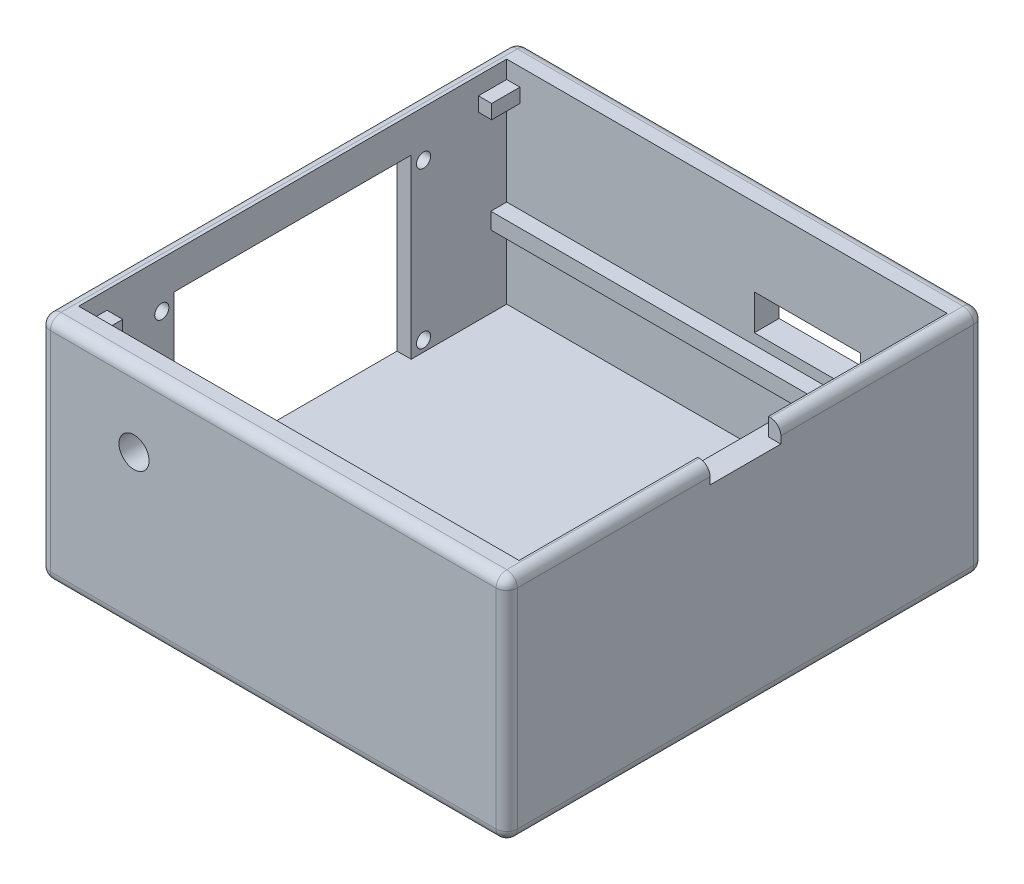
SolidWorks part; units mm, degrees
ref_plane "Front Plane" through (0, 0, 0) normal (0, 0, 1) x (1, 0, 0)
ref_plane "Top Plane" through (0, 0, 0) normal (0, 1, 0) x (1, 0, 0)
ref_plane "Right Plane" through (0, 0, 0) normal (1, 0, 0) x (0, 0, -1)
sketch "Sketch2" plane through (0, 0, 0) normal (0, 1, 0) x (1, 0, 0)
  line L0 (-60.5, 60.5) -> (-60.5, -60.5)
  line L1 (-67.5, 67.5) -> (67.5, 67.5)
  line L2 (-67.5, 67.5) -> (-67.5, -67.5)
  line L3 (-67.5, -67.5) -> (67.5, -67.5)
  line L4 (67.5, 67.5) -> (67.5, -67.5)
  line L5 (-67.5, 67.5) -> (67.5, -67.5) construction
  line L6 (-67.5, -67.5) -> (67.5, 67.5) construction
  line L7 (-60.5, -60.5) -> (60.5, -60.5)
  line L8 (60.5, 60.5) -> (60.5, -60.5)
  line L9 (-60.5, 60.5) -> (60.5, 60.5)
  point P0 (0, 0)
  dimension "D1" = 135
  dimension "D2" = 135
  dimension "D3" = 7
extrude "Boss-Extrude1" add sketch "Sketch2" along normal blind 65
extrude "Boss-Extrude2" add sketch "Sketch2<2>" along normal blind 5 contours L9 L0 L7 L8 region at (0, 0, 0)
sketch "Sketch2<2>" plane through (0, 0, 0) normal (0, 1, 0) x (1, 0, 0) same geometry as "Sketch2"
sketch "Sketch3" plane through (0, 0, -60.5) normal (0, 0, 1) x (1, 0, 0)
  line L1 (0, 0) -> (0, 65) construction
  line L2 (67.5, 0) -> (-67.5, 0) construction
  line L3 (60.5, 65) -> (-60.5, 65) construction
  line L4 (60.5, 65) -> (60.5, 5) construction
  line L5 (-60.5, 25.4157) -> (60.5, 25.4157)
  line L6 (-60.5, 25.4157) -> (-60.5, 30)
  line L7 (-60.5, 30) -> (60.5, 30)
  line L8 (60.5, 25.4157) -> (60.5, 30)
  line L9 (-60.5, 25.4157) -> (60.5, 30) construction
  line L10 (-60.5, 30) -> (60.5, 25.4157) construction
  line L11 (-60.5, 5) -> (60.5, 5) construction
  line L12 (-60.5, 65) -> (-60.5, 5) construction
  line L13 (9.5, 43) -> (39.5, 43)
  line L14 (9.5, 43) -> (9.5, 33)
  line L15 (9.5, 33) -> (39.5, 33)
  line L16 (39.5, 43) -> (39.5, 33)
  line L17 (9.5, 43) -> (39.5, 33) construction
  line L18 (9.5, 33) -> (39.5, 43) construction
  point P1 (0, 27.7078)
  point P16 (24.5, 38)
  dimension "D1" = 25
  dimension "D2" = 121
  dimension "D3" = 30
  dimension "D4" = 10
  dimension "D5" = 70
  dimension "D6" = 13
extrude "Boss-Extrude3" add sketch "Sketch3" along normal blind 4.5 contours L5 L8 L7 L6
extrude "Cut-Extrude1" cut sketch "Sketch3<3>" against normal through all contours L16 L13 L14 L15 region at (24.5, 38, -60.5)
sketch "Sketch3<3>" plane through (0, 0, -60.5) normal (0, 0, 1) x (1, 0, 0) same geometry as "Sketch3"
sketch "Sketch10" plane through (0, 0, 67.5) normal (0, 0, 1) x (1, 0, 0)
  circle A0 centre (-37.8514, 44.0831) radius 4.25
extrude "Cut-Extrude2" cut sketch "Sketch10" against normal blind 26.5 contours A0
sketch "Sketch11" plane through (-67.5, 0, 0) normal (-1, 0, 0) x (0, 0, 1)
  line L1 (-40, 5) -> (40, 5)
  line L2 (-40, 5) -> (-40, 55)
  line L3 (-40, 55) -> (40, 55)
  line L4 (40, 5) -> (40, 55)
  line L5 (-40, 5) -> (40, 55) construction
  line L6 (-40, 55) -> (40, 5) construction
  line L7 (-33.5, 55) -> (33.5, 55)
  line L8 (-33.5, 55) -> (-33.5, 5)
  line L9 (-33.5, 5) -> (33.5, 5)
  line L14 (0, 0) -> (0, 60) construction
  line L15 (-67.5, 0) -> (67.5, 0) construction
  line L16 (-67.5, 65) -> (67.5, 65) construction
  line L17 (0, 30) -> (67.5, 30) construction
  line L18 (67.5, 65) -> (67.5, 0) construction
  line L19 (33.5, 55) -> (33.5, 5)
  circle A0 centre (-37, 52) radius 2
  circle A1 centre (37, 52) radius 2
  circle A2 centre (37, 8) radius 2
  circle A3 centre (-37, 8) radius 2
  point P0 (0, 30)
  dimension "D2" = 4
  dimension "D1" = 3.5
extrude "Cut-Extrude3" cut sketch "Sketch11" against normal blind 26.5 contours L8 L7 L19 L9 | A0 | A2 | A1 | A3
sketch "Sketch12" plane through (0, 65, 0) normal (0, 1, 0) x (1, 0, 0)
  line L0 (67.5, -67.5) -> (67.5, 67.5) construction
  line L1 (60.5, 60.5) -> (67.5, 60.5)
  line L2 (60.5, 60.5) -> (60.5, -60.5)
  line L3 (60.5, -60.5) -> (67.5, -60.5)
  line L4 (67.5, 60.5) -> (67.5, -60.5)
extrude "Cut-Extrude4" cut sketch "Sketch12" against normal blind 5
sketch "Sketch13" plane through (0, 60, 0) normal (0, 1, 0) x (1, 0, 0)
  line L0 (64, 60.5) -> (64, -60.5)
  line L1 (67.5, 60.5) -> (60.5, 60.5) construction
  line L2 (60.5, -60.5) -> (67.5, -60.5) construction
  line L3 (64, -60.5) -> (67.5, -60.5)
  line L4 (67.5, -60.5) -> (67.5, 60.5)
  line L5 (67.5, 60.5) -> (64, 60.5)
extrude "Boss-Extrude4" add sketch "Sketch13" along normal blind 5
sketch "Sketch14" plane through (67.5, 0, 0) normal (1, 0, 0) x (0, 0, -1)
  line L0 (-10, 65) -> (10, 65)
  line L1 (-67.5, 65) -> (67.5, 65) construction
  line L2 (10, 65) -> (10, 60)
  line L3 (10, 60) -> (-10, 60)
  line L4 (-10, 60) -> (-10, 65)
  line L5 (-67.5, 65) -> (-67.5, 0) construction
  point P5 (0, 65)
  dimension "D1" = 57.5
  dimension "D2" = 5
extrude "Cut-Extrude5" cut sketch "Sketch14" against normal blind 5
sketch "Sketch15" plane through (-67.5, 0, 0) normal (-1, 0, 0) x (0, 0, 1)
  line L1 (-67.5, 0) -> (67.5, 0)
  line L2 (-67.5, 0) -> (-67.5, 65)
  line L3 (-67.5, 65) -> (67.5, 65)
  line L4 (67.5, 0) -> (67.5, 65)
extrude "Cut-Extrude6" cut sketch "Sketch15" against normal blind 3
sketch "Sketch16" plane through (0, 5, 0) normal (0, 1, 0) x (1, 0, 0)
  line L0 (-60.5, 0) -> (60.5, 0) construction
  line L1 (-60.5, 60.5) -> (-60.5, -60.5) construction
  line L2 (60.5, 60.5) -> (60.5, -60.5) construction
sketch "Sketch17" plane through (0, 0, 60.5) normal (0, 0, -1) x (-1, 0, 0)
  line L0 (0, 0) -> (0, 65) construction
  line L1 (-60.3877, 30) -> (60.5375, 30)
  line L2 (-60.3877, 30) -> (-60.3877, 25.5)
  line L3 (-60.3877, 25.5) -> (60.5375, 25.5)
  line L4 (60.5375, 30) -> (60.5375, 25.5)
  line L5 (60.5, 65) -> (-64, 65) construction
  point P12 (0, 4.8129)
  dimension "D1" = 4.5
  dimension "D2" = 25.5
extrude "Boss-Extrude5" add sketch "Sketch17" along normal blind 4.5 contours L2 L1 L4 L3
sketch "Sketch18" plane through (0, 0, 0) normal (1, 0, 0) x (0, 0, -1)
fillet "Fillet1" radius 3 3 edges at (67.5, 0, 0) (1.5, 0, 67.5) (1.5, 0, -67.5)
fillet "Fillet2" radius 3 9 edges at (66.6213, 0.8787, -66.6213) (-64.5, 34, -67.5) (-64.5, 0.8787, -66.6213) (-64.5, 0, 0) (-64.5, 0.8787, 66.6213) (66.6213, 0.8787, 66.6213) (67.5, 34, -67.5) (-64.5, 34, 67.5) (67.5, 34, 67.5)
fillet "Fillet3" radius 3 9 edges at (67.5, 65, -37.25) (66.6213, 65, -66.6213) (1.5, 65, -67.5) (-63.6213, 65, -66.6213) (-64.5, 65, 0) (-63.6213, 65, 66.6213) (1.5, 65, 67.5) (66.6213, 65, 66.6213) (67.5, 65, 37.25)
sketch "Sketch19" plane through (0, 0, -60.5) normal (0, 0, 1) x (1, 0, 0)
  line L0 (-60.5, 65) -> (-60.5, 30) construction
  line L1 (-60.5, 60) -> (-56.7558, 60)
  line L2 (-60.5, 60) -> (-60.5, 56)
  line L3 (-60.5, 56) -> (-56.7558, 56)
  line L4 (-56.7558, 60) -> (-56.7558, 56)
  dimension "D1" = 5
  dimension "D2" = 4
extrude "Boss-Extrude6" add sketch "Sketch19" along normal blind 8
sketch "Sketch20" plane through (0, 0, 60.5) normal (0, 0, -1) x (-1, 0, 0)
  line L0 (60.5, 65) -> (60.5, 30) construction
  line L1 (60.5, 60) -> (56.0522, 60)
  line L2 (60.5, 60) -> (60.5, 55.348)
  line L3 (60.5, 55.348) -> (56.0522, 55.348)
  line L4 (56.0522, 60) -> (56.0522, 55.348)
  dimension "D1" = 5
  dimension "D2" = 4.4478
extrude "Boss-Extrude7" add sketch "Sketch20" along normal blind 8
